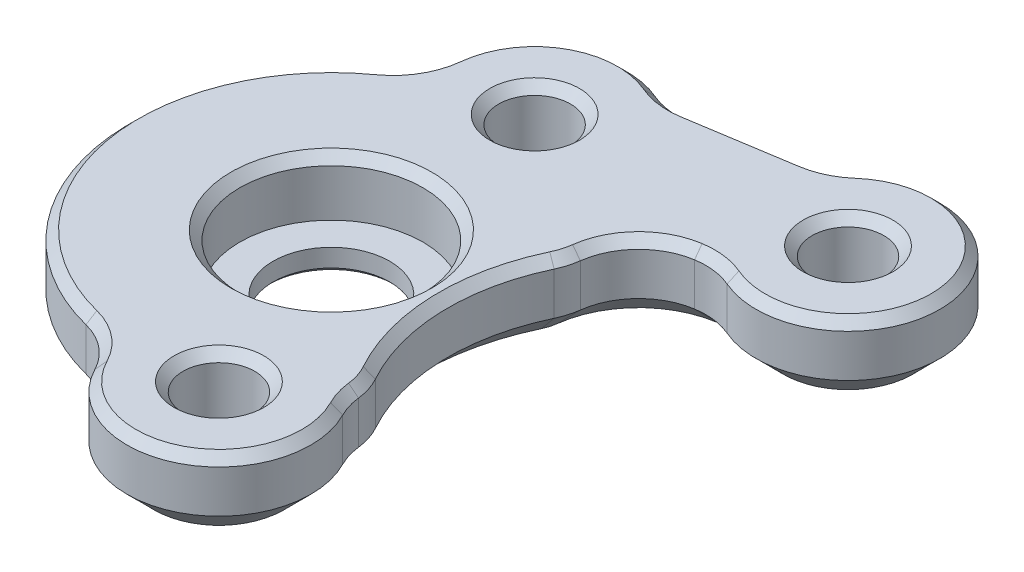
SolidWorks part; units mm, degrees
ref_plane "Front Plane" through (0, 0, 0) normal (0, 0, 1) x (1, 0, 0)
ref_plane "Top Plane" through (0, 0, 0) normal (0, 1, 0) x (1, 0, 0)
ref_plane "Right Plane" through (0, 0, 0) normal (1, 0, 0) x (0, 0, -1)
sketch "Sketch1" plane through (0, 0, 0) normal (0, 1, 0) x (1, 0, 0)
  circle A0 centre (0, 0) radius 9
  circle A1 centre (0, 0) radius 4.08
  dimension "D1" = 18
  dimension "D2" = 8.16
extrude "Boss-Extrude1" add sketch "Sketch1" along normal blind 3.5
sketch "Sketch2" plane through (0, 3.5, 0) normal (0, 1, 0) x (1, 0, 0)
  circle A0 centre (3.3433, -8.356) radius 1.6
  circle A1 centre (0.0612, 8.9998) radius 1.6
  circle A2 centre (3.3433, -8.356) radius 4.1
  circle A3 centre (0.0612, 8.9998) radius 4.1
  dimension "D1" = 2.5
extrude "Boss-Extrude2" add sketch "Sketch2" against normal blind 3.5
sketch "Sketch6" plane through (0, 0, 0) normal (0, -1, 0) x (-1, 0, 0)
  circle A0 centre (-14.2, 0) radius 9
  dimension "D1" = 18
  dimension "D2" = 14.2
extrude "Cut-Extrude2" cut sketch "Sketch6" against normal through all
sketch "Sketch3" plane through (0, 0, 0) normal (0, -1, 0) x (-1, 0, 0)
  circle A0 centre (-0.0612, 8.9998) radius 1.6
  arc A1 (-4.7701, -7.6319) -> (-1.8108, -8.8159) centre (0, 0) ccw construction
  arc A2 (1.5334, 8.8684) -> (-1.6538, 8.8467) centre (0, 0) ccw construction
  circle A4 centre (-3.3433, -8.356) radius 1.6
extrude "Cut-Extrude1" cut sketch "Sketch3" against normal blind 3.5
sketch "Sketch4" plane through (0, 0, 0) normal (0, -1, 0) x (-1, 0, 0)
  line L0 (-0.0612, 8.9998) -> (-12.1263, 10.9048) construction
  line L1 (-2.3537, 12.3989) -> (-8.898, 13.4322)
  line L3 (-5.8131, 6.8708) -> (-9.8338, 7.5057)
  circle A0 centre (-12.1263, 10.9048) radius 1.6
  arc A1 (-8.898, 13.4322) -> (-9.8338, 7.5057) centre (-12.1263, 10.9048) ccw
  arc A2 (-2.3537, 12.3989) -> (-4.047, 8.0388) centre (-0.0612, 8.9998) ccw
  arc A3 (-4.047, 8.0388) -> (-5.8131, 6.8708) centre (0, 0) ccw
  circle A5 centre (-12.1263, 10.9048) radius 4.1 construction
  point P4 (-12.1263, 10.9048)
  point P5 (-12.1263, 10.9048)
  point P8 (-7.2556, 11.7052)
  point P9 (-12.1263, 10.9048)
  point P10 (-8.0263, 10.9048)
  point P13 (-8.0263, 10.9048)
  point P17 (-8.0263, 10.9048)
  arc M5 (-4.047, 8.0388) -> (-7.1, 5.5308) centre (0, 0) ccw
  dimension "D2" = 3
  dimension "D1" = 2.5
extrude "Boss-Extrude3" add sketch "Sketch4" against normal blind 3.5 contours A0 M5 region at (9.8918, 0, -10.6162)
sketch "Sketch5" plane through (0, 0, 0) normal (0, -1, 0) x (-1, 0, 0)
  circle A0 centre (0, 0) radius 4.08
  circle A1 centre (0, 0) radius 2.6
  dimension "D1" = 5.2
  dimension "D2" = 8.16
extrude "Boss-Extrude4" add sketch "Sketch5" against normal blind 1
fillet "Fillet1" radius 3 7 edges at (-3.9373, 1.75, -8.0931) (-0.7102, 1.75, 8.9719) (9.8338, 1.75, -7.5057) (8.898, 1.75, -13.4322) (2.3537, 1.75, -12.3989) (7.1, 1.75, -5.5308) (7.1, 1.75, 5.5308)
fillet "Fillet9" radius 3 2 edges at (5.8131, 1.75, -6.8708) (6.7029, 1.75, 6.0059)
chamfer "倒角1" distance 1.2 angle 45 16 edges at (16.1761, 0, -11.5442) (8.7151, 0, -13.5234) (9.6878, 0, -7.3626) (5.6259, 0, -12.9156) (8.8438, 0, -7.3493) (2.4996, 0, -12.542) (7.1582, 0, -6.4755) (-2.0077, 0, -12.5396) (6.238, 0, -4.3017) (-4.406, 0, -8.2391) (5.2046, 0, 0.2865) (-8.8433, 0, 1.6723) (6.5641, 0, 4.9054) (-1.0932, 0, 9.279) (6.7966, 0, 5.9989) (5.2201, 0, 12.0012)
chamfer "倒角2" distance 0.2 angle 45 4 edges at (3.3433, 0, 9.956) (12.1263, 0, -12.5048) (0, 0, -2.6) (0.0612, 0, -7.3998)
chamfer "倒角3" distance 0.4 angle 45 20 edges at (12.1263, 3.5, -12.5048) (0, 3.5, 4.08) (0.0612, 3.5, -7.3998) (3.3433, 3.5, 9.956) (6.5641, 3.5, 4.9054) (6.7966, 3.5, 5.9989) (5.2201, 3.5, 12.0012) (-1.0932, 3.5, 9.279) (-8.8433, 3.5, 1.6723) (-4.406, 3.5, -8.2391) (-2.0077, 3.5, -12.5396) (2.4996, 3.5, -12.542) (5.6259, 3.5, -12.9156) (8.7151, 3.5, -13.5234) (16.1761, 3.5, -11.5442) (9.6878, 3.5, -7.3626) (8.8438, 3.5, -7.3493) (7.1582, 3.5, -6.4755) (6.238, 3.5, -4.3017) (5.2046, 3.5, 0.2865)
equation "\"D2@Sketch6\"=5.2+\"D1@Sketch6\"/2"
